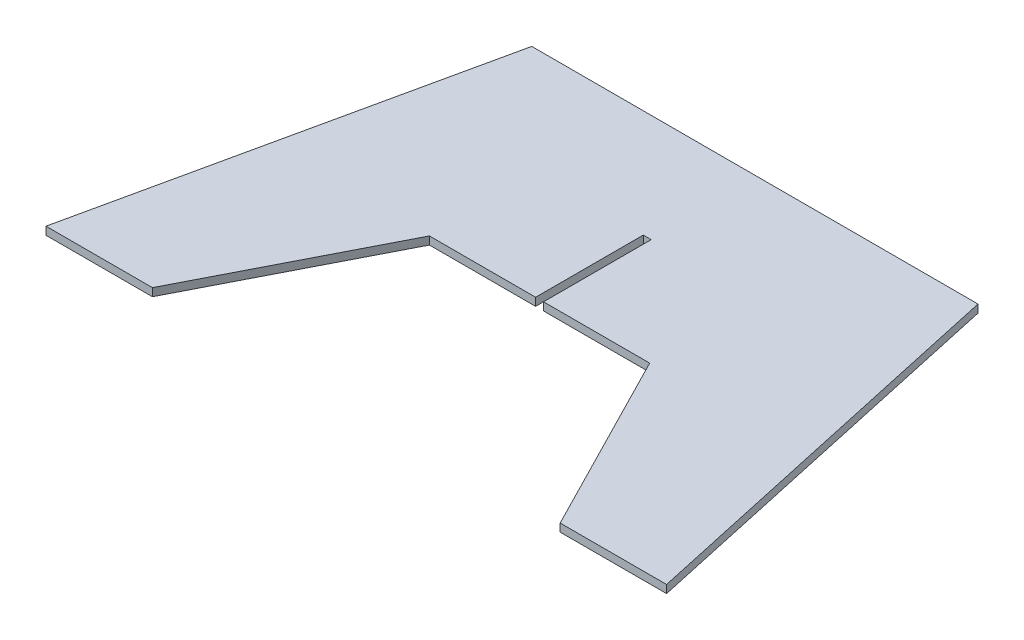
SolidWorks part; units mm, degrees
ref_plane "Front Plane" through (0, 0, 0) normal (0, 0, 1) x (1, 0, 0)
ref_plane "Top Plane" through (0, 0, 0) normal (0, 1, 0) x (1, 0, 0)
ref_plane "Right Plane" through (0, 0, 0) normal (1, 0, 0) x (0, 0, -1)
sketch "Sketch1" plane through (0, 0, 0) normal (0, 1, 0) x (1, 0, 0)
  line L0 (-22.25, 0) -> (-33.8636, 0)
  line L1 (-33.8636, 0) -> (-24.35, 43.5)
  line L2 (-24.35, 43.5) -> (24.35, 43.5)
  line L3 (24.35, 43.5) -> (33.8636, 0)
  line L4 (33.8636, 0) -> (22.25, 0)
  line L5 (22.25, 0) -> (12.0201, 20)
  line L6 (12.0201, 20) -> (-12.0201, 20)
  line L7 (-12.0201, 20) -> (-22.25, 0)
  line L8 (0, 43.5) -> (0, 20) construction
  line L9 (0, 20) -> (0, 0) construction
  line L10 (0, 43.5) -> (-22.25, 0) construction
  line L11 (0.4318, 31.75) -> (0.4318, 43.5) construction
  line L12 (0.4318, 20) -> (-0.4318, 20)
  line L13 (0.4318, 20) -> (0.4318, 31.75)
  line L14 (0.4318, 31.75) -> (-0.4318, 31.75)
  line L15 (-0.4318, 20) -> (-0.4318, 31.75)
  point P10 (0, 31.75)
  dimension "D1" = 67.7272
  dimension "D2" = 48.7
  dimension "D3" = 43.5
  dimension "D4" = 44.5
  dimension "D5" = 20
  dimension "D6" = 0.8636
extrude "Boss-Extrude1" add sketch "Sketch1" along normal blind 0.8636 contours L6 L15 L14 L13 L5 L4 L3 L2 L1 L0 L7 region at (-28.0568, 0, -0.8049)
